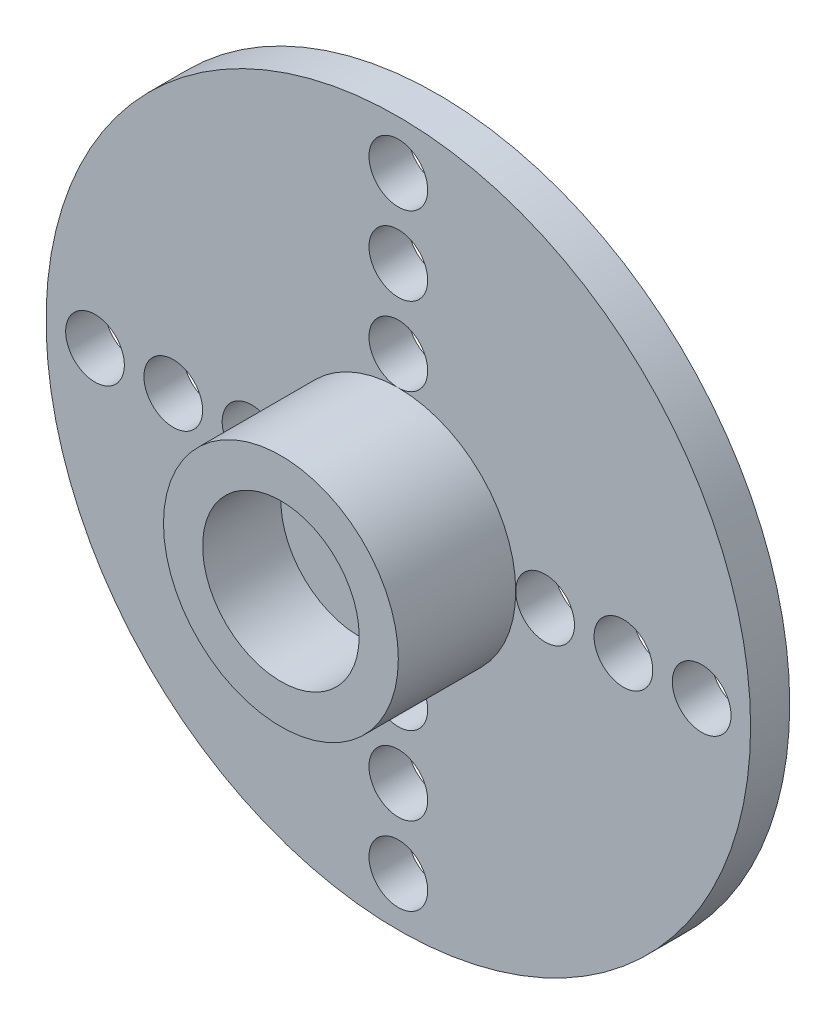
SolidWorks part; units mm, degrees
ref_plane "Front Plane" through (0, 0, 0) normal (0, 0, 1) x (1, 0, 0)
ref_plane "Top Plane" through (0, 0, 0) normal (0, 1, 0) x (1, 0, 0)
ref_plane "Right Plane" through (0, 0, 0) normal (1, 0, 0) x (0, 0, -1)
sketch "Sketch1" plane through (0, 0, 0) normal (0, 0, 1) x (1, 0, 0)
  line L0 (0, 0) -> (0, 4639.3744) construction
  line L1 (0, 0) -> (-4639.3744, 0) construction
  circle A0 centre (0, 0) radius 9
  circle A1 centre (0, 0) radius 3
  circle A2 centre (0, 0) radius 2
  dimension "D1" = 6
  dimension "D2" = 18
  dimension "D3" = 4
extrude "Boss-Extrude1" add sketch "Sketch1" along normal blind 1 contours A0 A1 region at (-8.7454, 0, 0)
extrude "Boss-Extrude2" add sketch "Sketch1<3>" along normal blind 4 contours A1 A2 region at (-2.9151, 0, 0)
sketch "Sketch1<3>" plane through (0, 0, 0) normal (0, 0, 1) x (1, 0, 0) same geometry as "Sketch1"
extrude "Boss-Extrude3" add sketch "Sketch1<4>" along normal blind 2 contours A2 region at (0, 0, 0)
sketch "Sketch1<4>" plane through (0, 0, 0) normal (0, 0, 1) x (1, 0, 0) same geometry as "Sketch1"
sketch "Sketch2" plane through (0, 0, 2) normal (0, 0, 1) x (1, 0, 0)
  circle A0 centre (0, 0) radius 0.75
  dimension "D1" = 1.5
extrude "Cut-Extrude1" cut sketch "Sketch2" against normal blind 2
sketch "Sketch3" plane through (0, 0, 1) normal (0, 0, 1) x (1, 0, 0)
  line L0 (0, 0) -> (0, 50000) construction
  line L1 (0, 0) -> (-50000, 0) construction
  circle A0 centre (3.75, 0) radius 0.75
  circle A1 centre (5.75, 0) radius 0.75
  circle A2 centre (7.75, 0) radius 0.75
  circle A3 centre (-3.75, 0) radius 0.75
  circle A4 centre (-5.75, 0) radius 0.75
  circle A5 centre (-7.75, 0) radius 0.75
  circle A6 centre (0, 3.75) radius 0.75
  circle A7 centre (0, 5.75) radius 0.75
  circle A8 centre (0, 7.75) radius 0.75
  circle A9 centre (0, -3.75) radius 0.75
  circle A10 centre (0, -5.75) radius 0.75
  circle A11 centre (0, -7.75) radius 0.75
  dimension "D1" = 1.5
  dimension "D2" = 1.5
  dimension "D3" = 1.5
  dimension "D7" = 1.5
  dimension "D4" = 3.75
  dimension "D5" = 2
  dimension "D6" = 2
  dimension "D8" = 3.75
  dimension "D9" = 2
  dimension "D10" = 2
extrude "Cut-Extrude2" cut sketch "Sketch3" against normal through all
